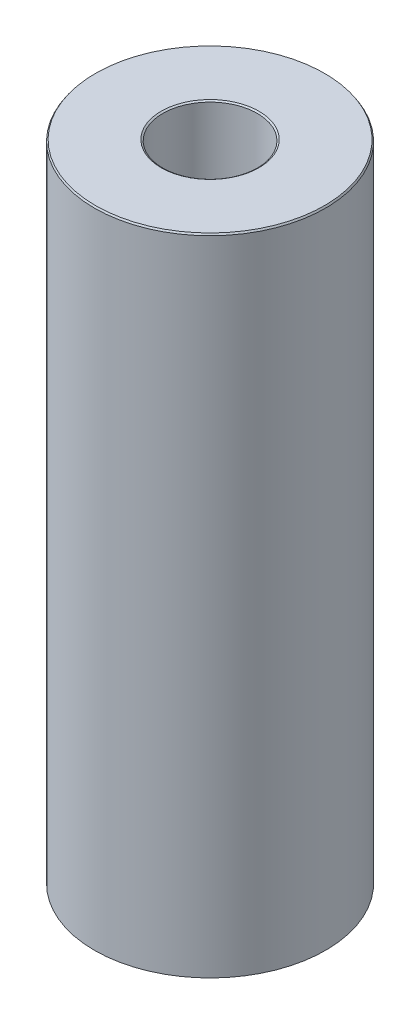
SolidWorks part; units mm, degrees
ref_plane "Front Plane" through (0, 0, 0) normal (0, 0, 1) x (1, 0, 0)
ref_plane "Top Plane" through (0, 0, 0) normal (0, 1, 0) x (1, 0, 0)
ref_plane "Right Plane" through (0, 0, 0) normal (1, 0, 0) x (0, 0, -1)
sketch "Sketch1" plane through (0, 0, 0) normal (0, 1, 0) x (1, 0, 0)
  circle A0 centre (0, 0) radius 17.5
  dimension "SLEEVE_OD" = 35
extrude "Boss-Extrude1" add sketch "Sketch1" along normal blind 97.6893
sketch "Sketch2" plane through (0, 0, 0) normal (0, 1, 0) x (1, 0, 0)
  circle A0 centre (0, 0) radius 7.162
  dimension "BORE_D" = 14.324
extrude "Cut-Extrude1" cut sketch "Sketch2" along normal through all
chamfer "Chamfer1" distance 0.2447 angle 33.809 4 edges at (0, 97.6893, 7.162) (0, 0, 7.162) (0, 0, 17.5) (0, 97.6893, 17.5) first distance on face at (0, 97.6893, 7.162) first distance on face at (0, 0, 7.162) first distance on face at (0, 97.6893, 17.5)
